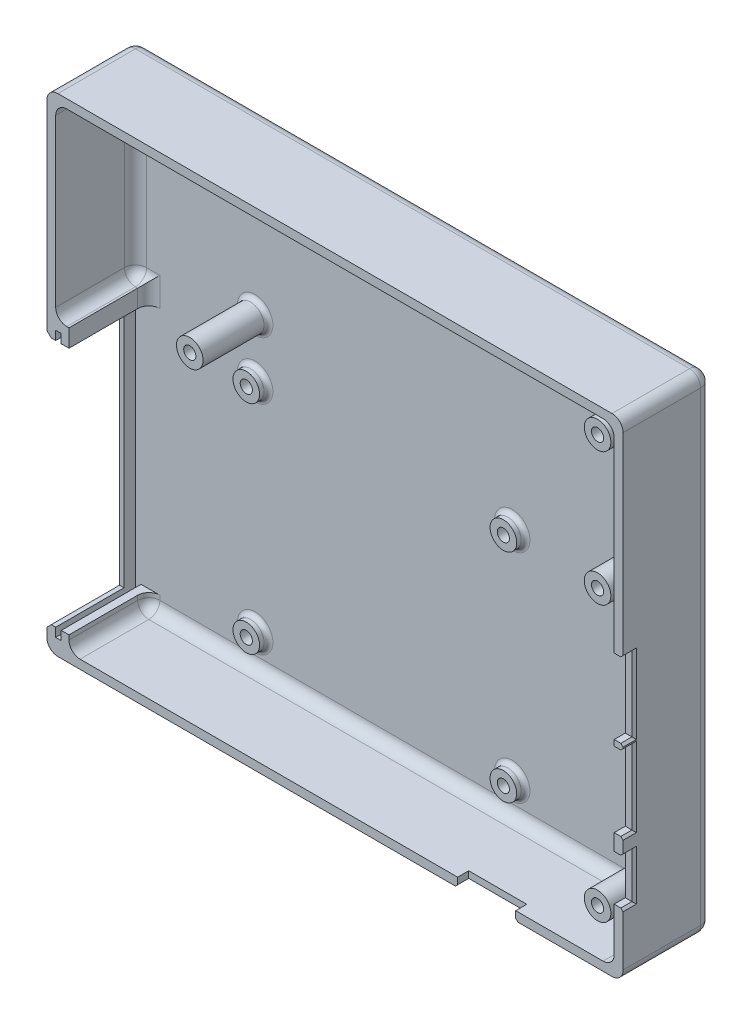
SolidWorks part; units mm, degrees
ref_plane "Plan de face" through (0, 0, 0) normal (0, 0, 1) x (1, 0, 0)
ref_plane "Plan de dessus" through (0, 0, 0) normal (0, 1, 0) x (1, 0, 0)
ref_plane "Plan de droite" through (0, 0, 0) normal (1, 0, 0) x (0, 0, -1)
sketch "Esquisse1" plane through (0, 0, 0) normal (0, 0, 1) x (1, 0, 0)
  line L1 (-87.7373, 71.0214) -> (42.2627, 71.0214)
  line L2 (-87.7373, 71.0214) -> (-87.7373, -38.9786)
  line L3 (-87.7373, -38.9786) -> (42.2627, -38.9786)
  line L4 (42.2627, 71.0214) -> (42.2627, -38.9786)
  dimension "D1" = 110
  dimension "D2" = 130
extrude "Boss.-Extru.1" add sketch "Esquisse1" along normal blind 2
sketch "Esquisse3" plane through (0, 0, 2) normal (0, 0, 1) x (1, 0, 0)
  line L2 (-87.7373, 71.0214) -> (-87.7373, -38.9786) construction
  line L3 (-87.7373, -38.9786) -> (42.2627, -38.9786) construction
  line L4 (42.2627, 71.0214) -> (-87.7373, 71.0214) construction
  circle A0 centre (33.2627, 62.0214) radius 1.375
  circle A1 centre (33.2627, 32.0214) radius 1.375
  circle A2 centre (33.2627, -29.9786) radius 1.375
  circle A3 centre (-58.7373, -29.9786) radius 1.375
  circle A4 centre (-0.7373, -29.9786) radius 1.375
  circle A5 centre (-0.7373, 19.0214) radius 1.375
  circle A6 centre (-58.7373, 19.0214) radius 1.375
  circle A7 centre (-58.7373, 32.0214) radius 1.375
  circle A8 centre (-58.7373, -29.9786) radius 3
  circle A9 centre (-0.7373, -29.9786) radius 3
  circle A10 centre (33.2627, -29.9786) radius 3
  circle A11 centre (-0.7373, 19.0214) radius 3
  circle A12 centre (33.2627, 32.0214) radius 3
  circle A13 centre (-58.7373, 32.0214) radius 3
  circle A14 centre (-58.7373, 19.0214) radius 3
  circle A15 centre (33.2627, 62.0214) radius 3
  dimension "D1" = 2.75
  dimension "D2" = 2.75
  dimension "D3" = 2.75
  dimension "D4" = 2.75
  dimension "D5" = 2.75
  dimension "D6" = 2.75
  dimension "D7" = 2.75
  dimension "D8" = 2.75
  dimension "D27" = 6
  dimension "D28" = 6
  dimension "D29" = 6
  dimension "D30" = 6
  dimension "D31" = 6
  dimension "D32" = 6
  dimension "D33" = 6
  dimension "D34" = 6
  dimension "D9" = 58
  dimension "D10" = 92
  dimension "D11" = 29
  dimension "D12" = 9
  dimension "D13" = 9
  dimension "D14" = 9
  dimension "D15" = 49
  dimension "D16" = 29
  dimension "D17" = 29
  dimension "D18" = 62
  dimension "D19" = 58
  dimension "D20" = 49
  dimension "D21" = 92
  dimension "D22" = 62
  dimension "D23" = 92
  dimension "D24" = 92
  dimension "D25" = 110
  dimension "D26" = 9
extrude "Boss.-Extru.2" add sketch "Esquisse3" along normal blind 2
sketch "Esquisse4" plane through (0, 0, 2) normal (0, 0, 1) x (1, 0, 0)
  circle A0 centre (-58.7373, 32.0214) radius 3
  circle A1 centre (-58.7373, 32.0214) radius 1.375
  circle A2 centre (33.2627, 62.0214) radius 3
  circle A3 centre (33.2627, 62.0214) radius 1.375
  circle A4 centre (33.2627, 32.0214) radius 1.375
  circle A5 centre (33.2627, 32.0214) radius 3
  circle A6 centre (33.2627, -29.9786) radius 3
  circle A7 centre (33.2627, -29.9786) radius 1.375
extrude "Boss.-Extru.3" add sketch "Esquisse4" along normal blind 14.75
fillet "Congé1" radius 1 8 edges at (36.2627, 62.0214, 2) (36.2627, 32.0214, 2) (-55.7373, -29.9786, 2) (36.2627, -29.9786, 2) (2.2627, -29.9786, 2) (2.2627, 19.0214, 2) (-55.7373, 19.0214, 2) (-55.7373, 32.0214, 2)
sketch "Esquisse5" plane through (0, 0, 2) normal (0, 0, 1) x (1, 0, 0)
  line L1 (-87.7373, 71.0214) -> (42.2627, 71.0214)
  line L2 (-87.7373, 71.0214) -> (-87.7373, -38.9786)
  line L3 (-87.7373, -38.9786) -> (42.2627, -38.9786)
  line L4 (42.2627, 71.0214) -> (42.2627, -38.9786)
  line L5 (-85.7373, 69.0214) -> (40.2627, 69.0214)
  line L6 (-85.7373, 69.0214) -> (-85.7373, -36.9786)
  line L7 (-85.7373, -36.9786) -> (40.2627, -36.9786)
  line L8 (40.2627, 69.0214) -> (40.2627, -36.9786)
  dimension "D1" = 2
  dimension "D2" = 2
  dimension "D3" = 2
  dimension "D4" = 2
extrude "Boss.-Extru.5" add sketch "Esquisse5" along normal blind 18
fillet "Congé3" radius 2.5 4 edges at (42.2627, 71.0214, 10) (42.2627, -38.9786, 10) (-87.7373, -38.9786, 10) (-87.7373, 71.0214, 10)
sketch "Esquisse6" plane through (0, 0, 20) normal (0, 0, 1) x (1, 0, 0)
  line L0 (40.2627, -36.9786) -> (40.2627, 69.0214) construction
  line L1 (40.2627, -24.5886) -> (42.2627, -24.5886)
  line L2 (40.2627, -24.5886) -> (40.2627, -14.2886)
  line L3 (40.2627, -14.2886) -> (42.2627, -14.2886)
  line L4 (42.2627, -24.5886) -> (42.2627, -14.2886)
  line L5 (42.2627, -36.4786) -> (42.2627, 68.5214) construction
  line L6 (-85.2373, -38.9786) -> (39.7627, -38.9786) construction
  line L7 (40.2627, -10.6086) -> (42.2627, -10.6086)
  line L8 (40.2627, -10.6086) -> (40.2627, 6.2714)
  line L9 (40.2627, 6.2714) -> (42.2627, 6.2714)
  line L10 (42.2627, -10.6086) -> (42.2627, 6.2714)
  line L11 (40.2627, 7.5814) -> (42.2627, 7.5814)
  line L12 (40.2627, 7.5814) -> (40.2627, 24.4614)
  line L13 (40.2627, 24.4614) -> (42.2627, 24.4614)
  line L14 (42.2627, 7.5814) -> (42.2627, 24.4614)
  line L15 (-85.7373, -36.9786) -> (40.2627, -36.9786) construction
  line L16 (4.9427, -36.9786) -> (18.0427, -36.9786)
  line L17 (4.9427, -36.9786) -> (4.9427, -38.9786)
  line L18 (4.9427, -38.9786) -> (18.0427, -38.9786)
  line L19 (18.0427, -36.9786) -> (18.0427, -38.9786)
  point P16 (41.2627, -24.5886)
  dimension "D1" = 14.39
  dimension "D2" = 24.69
  dimension "D3" = 28.37
  dimension "D4" = 45.25
  dimension "D5" = 46.56
  dimension "D6" = 63.44
  dimension "D7" = 37.32
  dimension "D8" = 24.22
extrude "Enlèv. mat.-Extru.1" cut sketch "Esquisse6" against normal blind 2.5
sketch "Esquisse7" plane through (0, 0, 20) normal (0, 0, 1) x (1, 0, 0)
  line L0 (-85.7373, 69.0214) -> (-85.7373, -36.9786) construction
  line L1 (-85.7373, -33.4786) -> (-87.7373, -33.4786)
  line L2 (-85.7373, -33.4786) -> (-85.7373, 22.5214)
  line L3 (-85.7373, 22.5214) -> (-87.7373, 22.5214)
  line L4 (-87.7373, -33.4786) -> (-87.7373, 22.5214)
  line L7 (-85.7373, -36.9786) -> (4.9427, -36.9786) construction
  dimension "D1" = 3.5
  dimension "D2" = 59.5
extrude "Enlèv. mat.-Extru.2" cut sketch "Esquisse7" against normal blind 15.4
fillet "Congé5" radius 2.5 8 edges at (41.5305, 70.2892, 0) (42.2627, 16.0214, 0) (41.5305, -38.2463, 0) (-22.7373, -38.9786, 0) (-87.005, -38.2463, 0) (-87.7373, 16.0214, 0) (-87.005, 70.2892, 0) (-22.7373, 71.0214, 0)
sketch "Esquisse9" plane through (-85.7373, 0, 0) normal (1, 0, 0) x (0, 0, -1)
  line L0 (-2, 69.0214) -> (-2, -36.9786) construction
  line L1 (-20, 22.5214) -> (-2, 22.5214)
  line L2 (-20, 22.5214) -> (-20, 26.5214)
  line L3 (-20, 26.5214) -> (-2, 26.5214)
  line L4 (-2, 22.5214) -> (-2, 26.5214)
  line L5 (-2, 24.5214) -> (-20, 24.5214)
  line L6 (-20, -33.4786) -> (-2, -33.4786)
  line L7 (-20, -33.4786) -> (-20, -36.9786)
  line L8 (-20, -36.9786) -> (-2, -36.9786)
  line L9 (-2, -33.4786) -> (-2, -36.9786)
  line L10 (-2, -35.4786) -> (-20, -35.4786)
  line M9 (-20, -36.9786) -> (-2, -36.9786)
  line M10 (-2, -36.9786) -> (-2, 69.0214)
  line M12 (-20, 69.0214) -> (-20, 22.5214)
  dimension "D1" = 18
  dimension "D2" = 2
  dimension "D3" = 2
  dimension "D4" = 4
extrude "Boss.-Extru.6" add sketch "Esquisse9" along normal blind 3 contours L5 L4 L3 M12 | L10 L7 M10 M9 region at (-85.7373, 25.5214, 11) region at (-85.7373, -36.2286, 11)
sketch "Esquisse11" plane through (0, 24.5214, 0) normal (0, -1, 0) x (1, 0, 0)
  line L0 (-82.7373, 2) -> (-85.7373, 2) construction
  line L1 (-82.7373, 20) -> (-84.4873, 20)
  line L2 (-82.7373, 20) -> (-82.7373, 2)
  line L3 (-82.7373, 2) -> (-84.4873, 2)
  line L4 (-84.4873, 20) -> (-84.4873, 2)
  line L6 (-82.7373, 20) -> (-85.7373, 20)
  line L7 (-82.7373, 20) -> (-82.7373, 2)
  line L8 (-82.7373, 2) -> (-85.7373, 2)
  line L9 (-85.7373, 20) -> (-85.7373, 2)
  line M5 (-85.7373, 2) -> (-82.7373, 2)
  line M6 (-82.7373, 2) -> (-82.7373, 20)
  line M7 (-82.7373, 20) -> (-85.7373, 20)
  dimension "D1" = 1.75
extrude "Boss.-Extru.7" add sketch "Esquisse11" along normal blind 2 contours L4 M7 M5 M6 region at (-83.6123, 24.5214, 11)
sketch "Esquisse12" plane through (0, -35.4786, 0) normal (0, 1, 0) x (1, 0, 0)
  line L0 (-84.4873, -2) -> (-84.4873, -20)
  line L1 (-82.7373, -2) -> (-85.7373, -2)
  line L2 (-82.7373, -2) -> (-82.7373, -20)
  line L3 (-82.7373, -20) -> (-85.7373, -20)
  line L4 (-85.7373, -2) -> (-85.7373, -20)
  line M5 (-85.7373, -20) -> (-82.7373, -20)
  line M6 (-82.7373, -20) -> (-82.7373, -2)
  line M7 (-82.7373, -2) -> (-85.7373, -2)
  dimension "D1" = 1.75
extrude "Boss.-Extru.8" add sketch "Esquisse12" along normal blind 2 contours L0 M7 M5 M6 region at (-83.6123, -35.4786, 11)
fillet "Congé7" radius 2.5 5 edges at (40.2627, -36.9786, 11) (-82.7373, -36.9786, 11) (-85.7373, 26.5214, 11) (-85.7373, 69.0214, 11) (40.2627, 69.0214, 11)
fillet "Congé8" radius 2.5 11 edges at (-82.7373, -33.9786, 2) (-82.005, -36.2463, 2) (-21.2373, -36.9786, 2) (39.5305, -36.2463, 2) (40.2627, 16.0214, 2) (39.5305, 68.2892, 2) (-22.7373, 69.0214, 2) (-85.005, 68.2892, 2) (-82.9873, 26.5214, 2) (-85.005, 27.2537, 2) (-85.7373, 47.7714, 2)
fillet "Congé9" radius 2.5 1 edges at (-82.7373, 25.7714, 2)
chamfer "Chanfrein1" distance 1 angle 45 3 edges at (-87.7373, -33.4786, 12.3) (-87.7373, -5.4786, 4.6) (-87.7373, 22.5214, 12.3)
chamfer "Chanfrein2" distance 0.5 angle 45 12 edges at (42.2627, 24.4614, 18.75) (42.2627, 16.0214, 17.5) (42.2627, 7.5814, 18.75) (42.2627, 6.2714, 18.75) (42.2627, -2.1686, 17.5) (42.2627, -10.6086, 18.75) (42.2627, -14.2886, 18.75) (42.2627, -19.4386, 17.5) (42.2627, -24.5886, 18.75) (4.9427, -38.9786, 18.75) (18.0427, -38.9786, 18.75) (11.4927, -38.9786, 17.5)
